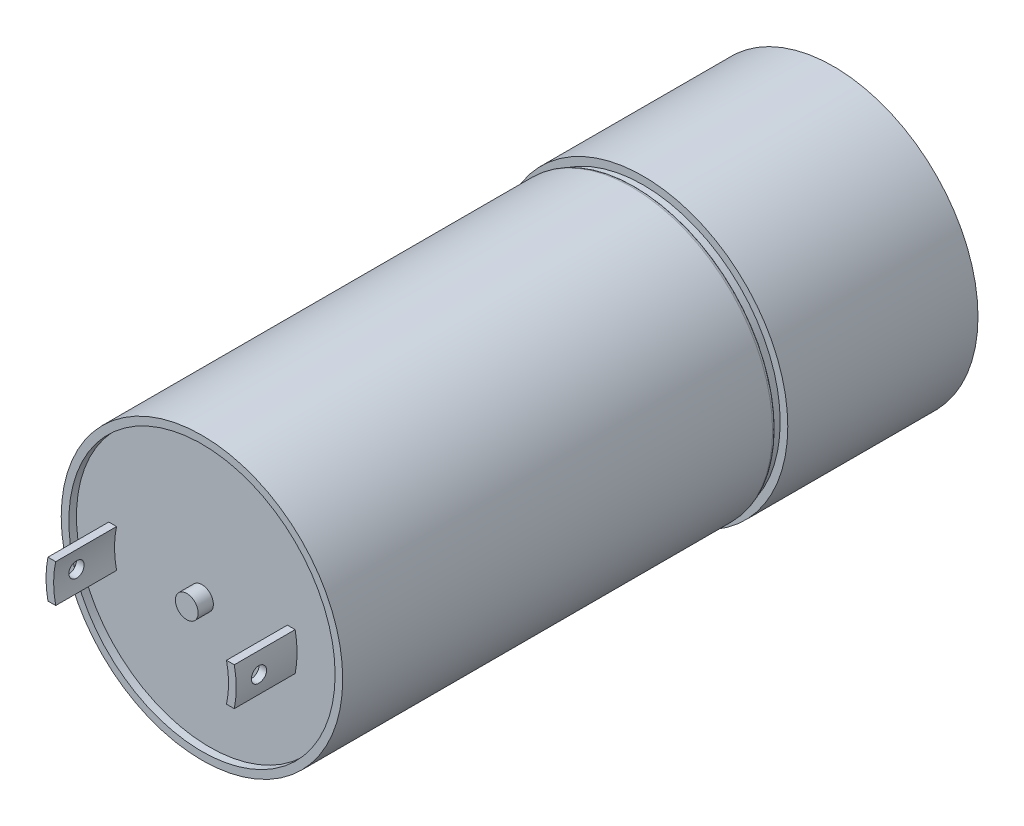
SolidWorks part; units mm, degrees
ref_plane "前视基准面" through (0, 0, 0) normal (0, 0, 1) x (1, 0, 0)
ref_plane "上视基准面" through (0, 0, 0) normal (0, 1, 0) x (1, 0, 0)
ref_plane "右视基准面" through (0, 0, 0) normal (1, 0, 0) x (0, 0, -1)
sketch "草图1" plane through (0, 0, 0) normal (0, 0, 1) x (1, 0, 0)
  circle A0 centre (0, 0) radius 18.5
  dimension "D1" = 37
extrude "凸台-拉伸1" add sketch "草图1" along normal blind 83
sketch "草图2" plane through (0, 0, 83) normal (0, 0, 1) x (1, 0, 0)
  circle A0 centre (0, 0) radius 1.5
  dimension "D1" = 3
extrude "凸台-拉伸2" add sketch "草图2" along normal blind 2
sketch "草图4" plane through (0, 0, 83) normal (0, 0, 1) x (1, 0, 0)
  line L0 (-12.2474, 2.5) -> (-11.225, 2.5)
  line L1 (-12.5, 0) -> (-11.5, 0) construction
  line L2 (-12.2474, -2.5) -> (-11.225, -2.5)
  line L3 (11.225, 2.5) -> (12.2474, 2.5)
  line L4 (11.5, 0) -> (12.5, 0) construction
  line L5 (11.225, -2.5) -> (12.2474, -2.5)
  arc A0 (-12.2474, 2.5) -> (-12.2474, -2.5) centre (0, 0) ccw
  arc A1 (-11.225, 2.5) -> (-11.225, -2.5) centre (0, 0) ccw
  arc A2 (12.2474, -2.5) -> (12.2474, 2.5) centre (0, 0) ccw
  arc A3 (11.225, -2.5) -> (11.225, 2.5) centre (0, 0) ccw
  dimension "D1" = 25
  dimension "D2" = 23
  dimension "D3" = 5
extrude "凸台-拉伸3" add sketch "草图4" along normal blind 8
sketch "草图6" plane through (0, 0, 0) normal (1, 0, 0) x (0, 0, -1)
  line L0 (-91, 0) -> (-83, 0) construction
  line L1 (-91, 2.5) -> (-91, -2.5) construction
  line L2 (-83, 18.5) -> (-83, -18.5) construction
  circle A0 centre (-88, 0) radius 1
  dimension "D1" = 2
  dimension "D2" = 3
extrude "切除-拉伸2" cut sketch "草图6" against normal up to next and the other way up to next
sketch "草图7" plane through (0, 0, 0) normal (0, 0, -1) x (-1, 0, 0)
  line L0 (0, 0) -> (15.5, 0) construction
  circle A0 centre (15.5, 0) radius 1.5
  circle A1 centre (0, 0) radius 15.5 construction
  circle A2 centre (7.75, -13.4234) radius 1.5
  circle A3 centre (-7.75, -13.4234) radius 1.5
  circle A4 centre (-15.5, 0) radius 1.5
  circle A5 centre (-7.75, 13.4234) radius 1.5
  circle A6 centre (7.75, 13.4234) radius 1.5
  point P18 (0, 0)
  dimension "D1" = 3
  dimension "D2" = 31
  dimension "D3" = 6
extrude "切除-拉伸3" cut sketch "草图7" against normal blind 10
sketch "草图8" plane through (0, 0, 0) normal (0, 0, -1) x (-1, 0, 0)
  line L0 (0, 0) -> (0, 18.5) construction
  circle A0 centre (0, 7) radius 6
  circle A1 centre (0, 0) radius 18.5 construction
  dimension "D1" = 7
  dimension "D2" = 12
extrude "凸台-拉伸4" add sketch "草图8" along normal blind 5
sketch "草图10" plane through (0, 0, -5) normal (0, 0, -1) x (-1, 0, 0)
  circle A0 centre (0, 7) radius 3
  dimension "D1" = 6
extrude "切除-拉伸4" cut sketch "草图10" against normal blind 20
ref_plane "基准面1" through (0, 0, 25) normal (0, 0, -1) x (-1, 0, 0)
sketch "草图11" plane through (0, 0, 25) normal (0, 0, -1) x (-1, 0, 0)
  circle A0 centre (0, 0) radius 18
  circle A1 centre (0, 0) radius 18.5
extrude "切除-拉伸5" cut sketch "草图11" against normal blind 1
sketch "草图12" plane through (0, 0, 25) normal (0, 0, -1) x (-1, 0, 0)
  circle A0 centre (0, 0) radius 19
  circle A1 centre (0, 0) radius 18.5
extrude "凸台-拉伸5" add sketch "草图12" along normal up to surface (25 mm away) up to face at (18.5, 0, 0)
fillet "圆角1" radius 0.5 1 edges at (-18.5, 0, 26)
sketch "草图13" plane through (0, 0, 83) normal (0, 0, 1) x (1, 0, 0)
  circle A1 centre (0, 0) radius 17.5
  dimension "D1" = 35
extrude "切除-拉伸6" cut sketch "草图13" against normal blind 1
